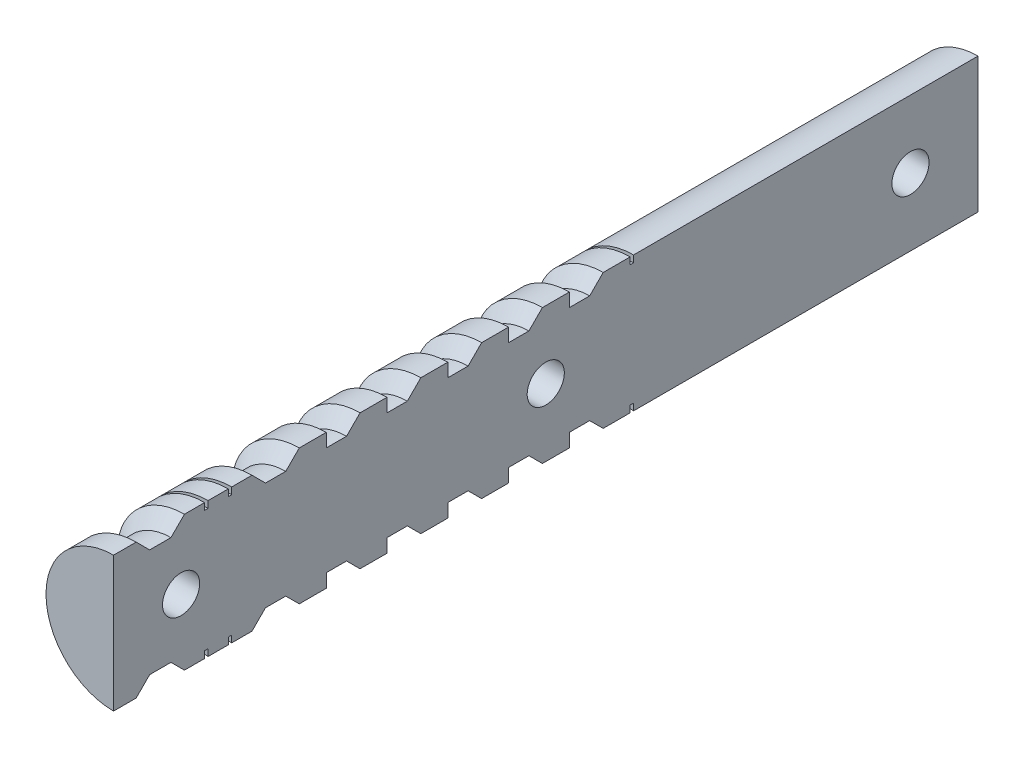
SolidWorks part; units mm, degrees
ref_plane "Front Plane" through (0, 0, 0) normal (0, 0, 1) x (1, 0, 0)
ref_plane "Top Plane" through (0, 0, 0) normal (0, 1, 0) x (1, 0, 0)
ref_plane "Right Plane" through (0, 0, 0) normal (1, 0, 0) x (0, 0, -1)
sketch "Sketch1" plane through (0, 0, 0) normal (0, 0, 1) x (1, 0, 0)
  line L1 (-14.25, -11.5) -> (14.25, -11.5)
  line L2 (-14.25, -11.5) -> (-14.25, 11.5)
  line L3 (-14.25, 11.5) -> (14.25, 11.5)
  line L4 (14.25, -11.5) -> (14.25, 11.5)
  line L5 (-14.25, -11.5) -> (14.25, 11.5) construction
  line L6 (-14.25, 11.5) -> (14.25, -11.5) construction
  point P0 (0, 0)
  dimension "D1" = 23
  dimension "D2" = 28.5
extrude "Centre block" add sketch "Sketch1" along normal blind 128
sketch "Sketch3" plane through (0, 0, 0) normal (0, 0, -1) x (-1, 0, 0)
  line L0 (-14.25, 11.5) -> (14.25, 11.5) construction
  line L1 (-10, 11.5) -> (10, 11.5)
  arc A0 (10, 11.5) -> (-10, 11.5) centre (0, 11.5) ccw
  dimension "D1" = 20
extrude "top cylinder" add sketch "Sketch3" against normal blind 90 and the other way blind 7
ref_plane "top" through (0, 11.5, 0) normal (0, 1, 0) x (1, 0, 0)
ref_axis "Axis3" through (0, 11.5, -7) along (0, 0, 1)
sketch "Sketch9" plane through (0, 11.5, 0) normal (0, 1, 0) x (1, 0, 0)
  line L0 (10, 0) -> (10, -90) construction
  line L1 (10, -78) -> (10, -81.8886)
  line L2 (10, -74.0526) -> (10, -73.5)
  line L3 (10, 0) -> (23.1871, 0)
  line L4 (23.1871, -74.0526) -> (23.1871, 0)
  line L5 (14.25, 0) -> (10, 0) construction
  line L6 (10, -8.5) -> (9.5, -8.5)
  line L7 (10, -11.5) -> (8, -13.5)
  line L8 (10, -8) -> (9.5, -8)
  line L9 (9.5, -8.5) -> (9.5, -8)
  line L10 (10, -8) -> (10, 0)
  line L11 (8, -13.5) -> (8, -16.5)
  line L12 (8, -16.5) -> (10, -18.5)
  line L13 (10, -11.5) -> (10, -8.5)
  line L14 (10, -21.5) -> (10, -18.5)
  line L15 (10, -22) -> (9.5, -22)
  line L16 (10, -25) -> (10, -22)
  line L17 (10, -21.5) -> (9.5, -21.5)
  line L18 (9.5, -22) -> (9.5, -21.5)
  line L19 (10, -25) -> (9.5, -25)
  line L20 (8, -60.3) -> (8, -58.5)
  line L21 (10, -25.5) -> (9.5, -25.5)
  line L22 (9.5, -25) -> (9.5, -25.5)
  line L23 (10, -28.5) -> (8, -30.5)
  line L24 (8, -30.5) -> (8, -33.5)
  line L25 (8, -33.5) -> (10, -35.5)
  line L26 (10, -28.5) -> (10, -25.5)
  line L27 (8, -48.5) -> (8, -51.5)
  line L28 (8, -41.5) -> (10, -43.5)
  line L29 (10, -38.5) -> (10, -35.5)
  line L30 (8, -58.5) -> (10, -58.5)
  line L31 (8, -51.5) -> (10, -53.5)
  line L34 (8, -61.5) -> (10, -63.5)
  line L35 (8, -60.3) -> (8, -61.5)
  line L36 (8, -48.5) -> (10, -48.5)
  line L37 (8, -71.5) -> (10, -73.5)
  line L38 (8, -70.3) -> (8, -71.5)
  line L39 (10, -68.5) -> (10, -63.5)
  line L40 (10, -58.5) -> (10, -53.5)
  line L41 (10, -48.5) -> (10, -43.5)
  line L42 (10, -78) -> (9.5, -78)
  line L43 (8, -41.5) -> (8, -38.5)
  line L44 (10, -74.0526) -> (10, -77.5)
  line L45 (10, -81.8886) -> (23.1871, -81.8886)
  line L46 (23.1871, -74.0526) -> (23.1871, -81.8886)
  line L47 (10, -77.5) -> (9.5, -77.5)
  line L48 (9.5, -78) -> (9.5, -77.5)
  line L52 (8, -38.5) -> (10, -38.5)
  line L54 (8, -70.3) -> (8, -68.5)
  line L55 (8, -68.5) -> (10, -68.5)
  point P52 (8, -38.5)
  dimension "D1" = 0.5
  dimension "D2" = 0.5
  dimension "D3" = 8
  dimension "D4" = 3
  dimension "D5" = 2
  dimension "D6" = 3
  dimension "D7" = 2
  dimension "D8" = 2
  dimension "D9" = 0.5
  dimension "D10" = 0.5
  dimension "D11" = 3
  dimension "D12" = 0.5
  dimension "D13" = 3
  dimension "D14" = 2
  dimension "D15" = 3
  dimension "D16" = 2
  dimension "D17" = 3
  dimension "D18" = 3
  dimension "D19" = 2
  dimension "D20" = 3
  dimension "D22" = 0.5
  dimension "D23" = 4
  dimension "D21" = 4
revolve "Cut-Revolve2" cut sketch "Sketch9" angle 180 about axis through (0, 11.5, -7) along (0, 0, 1)
sketch "Sketch4" plane through (0, 11.5, 0) normal (0, -1, 0) x (1, 0, 0)
  line L1 (10, -7) -> (-10, -7) construction
  line L3 (-3.25, -7) -> (-3.25, -2)
  line L4 (10, 0) -> (-10, 0) construction
  line L5 (-5.25, 0) -> (-10, 0)
  line L6 (-10, 0) -> (-10, -7)
  line L7 (-10, -7) -> (-10, 0) construction
  line L8 (-10, -7) -> (-3.25, -7)
  line L9 (3.75, -7) -> (3.75, -2)
  line L10 (-14.25, 0) -> (14.25, 0) construction
  line L11 (5.75, 0) -> (10, 0)
  line L12 (10, 0) -> (10, -7)
  line L13 (10, -7) -> (3.75, -7)
  arc A0 (5.75, 0) -> (3.75, -2) centre (5.75, -2) ccw
  arc A1 (-3.25, -2) -> (-5.25, 0) centre (-5.25, -2) ccw
  point P21 (3.75, 0)
  point P25 (-3.25, 0)
  dimension "D3" = 2
  dimension "D1" = 3.25
  dimension "D2" = 7
extrude "nose" cut sketch "Sketch4" against normal through all
sketch "Sketch5" plane through (14.25, 0, 0) normal (1, 0, 0) x (0, 0, -1)
  line L0 (-128, 11.5) -> (0, 11.5) construction
  line L1 (-128, -11.5) -> (-128, 11.5) construction
  line L2 (-101, 11.5) -> (-81, 11.5)
  arc A0 (-81, 11.5) -> (-101, 11.5) centre (-91, 11.5) ccw
  dimension "D1" = 20
  dimension "D2" = 37
extrude "t cross" add sketch "Sketch5" against normal up to surface (28.5 mm away) up to face at (-14.25, 0, 64)
sketch "Sketch6" plane through (0, 0, 0) normal (0, 0, -1) x (-1, 0, 0)
  line L0 (14.25, -11.5) -> (-14.25, -11.5) construction
  circle A0 centre (0, 0.5) radius 12
  dimension "D1" = 24
  dimension "D2" = 12
extrude "Barrel" add sketch "Sketch6" along normal blind 7 contours A0
ref_axis "Axis1" through (0, 0.5, -37.165) along (0, 0, 1)
sketch "Sketch2" plane through (0, 0, 0) normal (0, 0, -1) x (-1, 0, 0)
  line L0 (14.25, 11.5) -> (14.25, -11.5) construction
  line L1 (14.25, 10) -> (14.25, -10)
  arc A0 (14.25, -10) -> (14.25, 10) centre (14.25, 0) ccw
  dimension "D1" = 20
extrude "side cylinder" add sketch "Sketch2" against normal up to surface (128 mm away) up to face at (0, 0, 128)
ref_axis "side axis" through (-14.25, 0, 135.3823) along (0, 0, -1)
ref_plane "side" through (-14.25, 0, 0) normal (1, 0, 0) x (0, 0, -1)
sketch "Sketch7" plane through (-14.25, 0, 0) normal (1, 0, 0) x (0, 0, -1)
  line L0 (-51, -10) -> (-51, -9)
  line L1 (0, -10) -> (-51, -10)
  line L2 (0, -10) -> (0, -14.8124)
  line L3 (0, -14.8124) -> (-117.5, -14.8124)
  line L4 (-117.5, -14.8124) -> (-124.65, -14.8124)
  line L5 (-51, -9) -> (-51.5, -9)
  line L6 (-51.5, -9) -> (-51.5, -10)
  line L7 (-51.5, -10) -> (-55.5, -10)
  line L8 (-60.5, -10) -> (-64.5, -10)
  line L9 (-57.5, -8) -> (-55.5, -10)
  line L10 (-66.5, -8) -> (-64.5, -10)
  line L11 (-57.5, -8) -> (-58.7748, -8)
  line L12 (-58.7748, -8) -> (-60.5, -8)
  line L13 (-66.5, -8) -> (-67.7748, -8)
  line L14 (-60.5, -8) -> (-60.5, -10)
  line L15 (-75.5, -8) -> (-73.5, -10)
  line L16 (-75.5, -8) -> (-76.7748, -8)
  line L18 (-84.5, -8) -> (-82.5, -10)
  line L19 (-84.5, -8) -> (-85.7748, -8)
  line L21 (-93.5, -8) -> (-91.5, -10)
  line L22 (-93.5, -8) -> (-94.7748, -8)
  line L24 (-102.5, -8) -> (-100.5, -10)
  line L25 (-102.5, -8) -> (-105.5, -8)
  line L26 (-111, -10) -> (-114, -10)
  line L27 (-69.5, -10) -> (-73.5, -10)
  line L28 (-78.5, -10) -> (-82.5, -10)
  line L29 (-87.5, -10) -> (-91.5, -10)
  line L30 (-96.5, -10) -> (-100.5, -10)
  line L31 (-107.5, -10) -> (-110.5, -10)
  line L32 (-105.5, -8) -> (-107.5, -10)
  line L33 (-114.5, -10) -> (-117.5, -10)
  line L34 (-67.7748, -8) -> (-69.5, -8)
  line L35 (-110.5, -10) -> (-110.5, -9)
  line L36 (-110.5, -9) -> (-111, -9)
  line L37 (-111, -10) -> (-111, -9)
  line L38 (-117.5, -10) -> (-119.5, -8)
  line L39 (-114, -10) -> (-114, -9)
  line L40 (-114, -9) -> (-114.5, -9)
  line L41 (-114.5, -10) -> (-114.5, -9)
  line L42 (-119.5, -8) -> (-122.65, -8)
  line L43 (-122.65, -8) -> (-124.65, -10)
  line L45 (-69.5, -8) -> (-69.5, -10)
  line L46 (-124.65, -14.8124) -> (-124.65, -10)
  line L48 (-76.7748, -8) -> (-78.5, -8)
  line L49 (-78.5, -8) -> (-78.5, -10)
  line L53 (-85.7748, -8) -> (-87.5, -8)
  line L56 (-87.5, -8) -> (-87.5, -10)
  line L57 (-94.7748, -8) -> (-96.5, -8)
  line L58 (-96.5, -8) -> (-96.5, -10)
  point P49 (-60.5, -8)
  dimension "D1" = 51
  dimension "D2" = 0.5
  dimension "D3" = 1
  dimension "D4" = 3
  dimension "D5" = 2
  dimension "D6" = 4
  dimension "D8" = 2
  dimension "D9" = 0.5
  dimension "D10" = 0.5
  dimension "D11" = 3
  dimension "D12" = 3
  dimension "D13" = 3.15
  dimension "D14" = 3
  dimension "D15" = 2
  dimension "D16" = 2
  dimension "D17" = 4
  dimension "D7" = 6
revolve "Cut-Revolve1" cut sketch "Sketch7" angle 180 about axis through (-14.25, 0, 135.3823) along (0, 0, -1)
sketch "Sketch8" plane through (0, 0, 128) normal (0, 0, 1) x (1, 0, 0)
  circle A0 centre (0, 0) radius 2.75
  dimension "D1" = 5.5
extrude "Back hole" cut sketch "Sketch8" against normal blind 5
sketch "Sketch12" plane through (0, -11.5, 0) normal (0, -1, 0) x (1, 0, 0)
  line L0 (0, -37.165) -> (0, 140.8383) construction
  line L1 (-2.5, 118) -> (2.5, 118)
  line L2 (-2.5, 118) -> (-2.5, 38)
  line L3 (-2.5, 38) -> (2.5, 38)
  line L4 (2.5, 118) -> (2.5, 38)
  line L5 (-14.25, 128) -> (14.25, 128) construction
  dimension "D1" = 5
  dimension "D2" = 2.5
  dimension "D3" = 10
  dimension "D4" = 80
extrude "Cut-Extrude4" cut sketch "Sketch12" against normal blind 5
ref_axis "Axis5" through (-14.25, 11.5, 91) along (1, 0, 0)
sketch "Sketch15" plane through (14.25, 0, 0) normal (1, 0, 0) x (0, 0, -1)
  circle A0 centre (-91, 11.5) radius 2.75
  circle A1 centre (-91, -5.5) radius 2.75
  dimension "D1" = 5.5
  dimension "D2" = 2
extrude "Cut-Extrude6" cut sketch "Sketch15" against normal blind 10
sketch "Sketch16" plane through (0, 0, -7) normal (0, 0, -1) x (-1, 0, 0)
  circle A0 centre (0, 0) radius 6.5
  dimension "D1" = 13
fillet "Fillet2" radius 1 6 edges at (14.25, -11.5, 64) (-14.25, -11.5, 64) (-14.25, 11.5, 40.5) (-14.25, 11.5, 114.5) (14.25, 11.5, 40.5) (14.25, 11.5, 114.5)
extrude "Cut-Extrude7" cut sketch "Sketch16" against normal blind 20
sketch "Sketch17" [suppressed] plane through (0, 0, 0) normal (0, 0, -1) x (-1, 0, 0)
  line L0 (14.25, 12.65) -> (14.25, -12.65) construction
  line L1 (14.25, -11.5) -> (21.8493, -11.5)
  line L2 (14.25, -11.5) -> (14.25, -6.5)
  line L3 (14.25, -6.5) -> (21.8493, -6.5)
  line L4 (21.8493, -11.5) -> (21.8493, -6.5)
  line L5 (13.25, -11.5) -> (0, -11.5) construction
  arc A0 (14.25, -10) -> (14.25, 10) centre (14.25, 0) ccw construction
  dimension "D1" = 5
extrude "Boss-Extrude1" [suppressed] add sketch "Sketch17" against normal blind 0.3
pattern_linear "LPattern1" [suppressed] count 11 spacing 5.07 of bodies 120
sketch "Sketch18" [suppressed] plane through (0, 0, 51.5) normal (0, 0, -1) x (-1, 0, 0)
  line L0 (14.25, 12.65) -> (14.25, -12.65) construction
  line L1 (14.25, -11.4537) -> (21.8493, -11.4537)
  line L2 (14.25, -11.4537) -> (14.25, -6.5)
  line L3 (14.25, -6.5) -> (21.8493, -6.5)
  line L4 (21.8493, -11.4537) -> (21.8493, -6.5)
  line L5 (21.8493, -11.5) -> (21.8493, -6.5) construction
  arc A0 (21.8493, -6.5) -> (14.25, 10) centre (14.25, 0) ccw construction
extrude "Boss-Extrude2" [suppressed] add sketch "Sketch18" against normal blind 0.3
pattern_linear "LPattern2" [suppressed] count 2 spacing 3.7 of bodies 122
pattern_linear "LPattern3" [suppressed] count 6 spacing 9 of bodies 123
sketch "Sketch19" [suppressed] plane through (0, 0, 110.5) normal (0, 0, 1) x (1, 0, 0)
  line L1 (-14.25, -11.4537) -> (-21.8493, -11.4537)
  line L2 (-14.25, -11.4537) -> (-14.25, -6.5)
  line L3 (-14.25, -6.5) -> (-21.8493, -6.5)
  line L4 (-21.8493, -11.4537) -> (-21.8493, -6.5)
extrude "Boss-Extrude3" [suppressed] add sketch "Sketch19" along normal blind 0.3 from offset 2.95 offset against normal yes
pattern_linear "LPattern4" [suppressed] count 2 spacing 2.6 of bodies 125
pattern_linear "LPattern5" [suppressed] count 3 spacing 3.5 of bodies 126
pattern_linear "LPattern6" [suppressed] count 2 spacing 17.5 of bodies 127
sketch "Sketch20" [suppressed] plane through (0, 0, -7) normal (0, 0, -1) x (-1, 0, 0)
  line L0 (13.25, -11.5) -> (0, -11.5) construction
  line L1 (-11.9896, 0) -> (-6.4896, 0)
  line L2 (-11.9896, 0) -> (-11.9896, -11.5)
  line L3 (-11.9896, -11.5) -> (12, -11.5)
  line L4 (12, 0) -> (12, -11.5)
  line L5 (6.5, 0) -> (12, 0)
  arc A0 (-4.7958, 11.5) -> (0, -11.5) centre (0, 0.5) ccw construction
  arc A1 (-6.4896, 0) -> (6.5, 0) centre (0.0052, 0) ccw
extrude "Boss-Extrude4" [suppressed] add sketch "Sketch20" against normal blind 0.3
pattern_linear "LPattern7" [suppressed] count 2 spacing 3.5 along (0, 0, 1) of bodies 129
sketch "Sketch21" plane through (-14.25, 0, 0) normal (-1, 0, 0) x (0, 0, 1)
  line L1 (-12.1946, 24.7848) -> (140.3905, 24.7848)
  line L2 (-12.1946, 24.7848) -> (-12.1946, -18.054)
  line L3 (-12.1946, -18.054) -> (140.3905, -18.054)
  line L4 (140.3905, 24.7848) -> (140.3905, -18.054)
extrude "Cut-Extrude12" cut sketch "Sketch21" against normal through all
sketch "Sketch24" plane through (-14.25, 0, 0) normal (1, 0, 0) x (0, 0, -1)
  line L0 (-135.3823, 0) -> (12.8715, 0) construction
  line L1 (-128, -10) -> (-128, 10) construction
  line L2 (0, -10) -> (0, 10) construction
  circle A0 centre (-118, 0) radius 2.75
  circle A1 centre (-64, 0) radius 2.75
  circle A2 centre (-10, 0) radius 2.75
  dimension "D1" = 5.5
  dimension "D2" = 5.5
  dimension "D3" = 5.5
  dimension "D4" = 10
  dimension "D5" = 54
  dimension "D6" = 10
extrude "Cut-Extrude13" cut sketch "Sketch24" against normal blind 5
